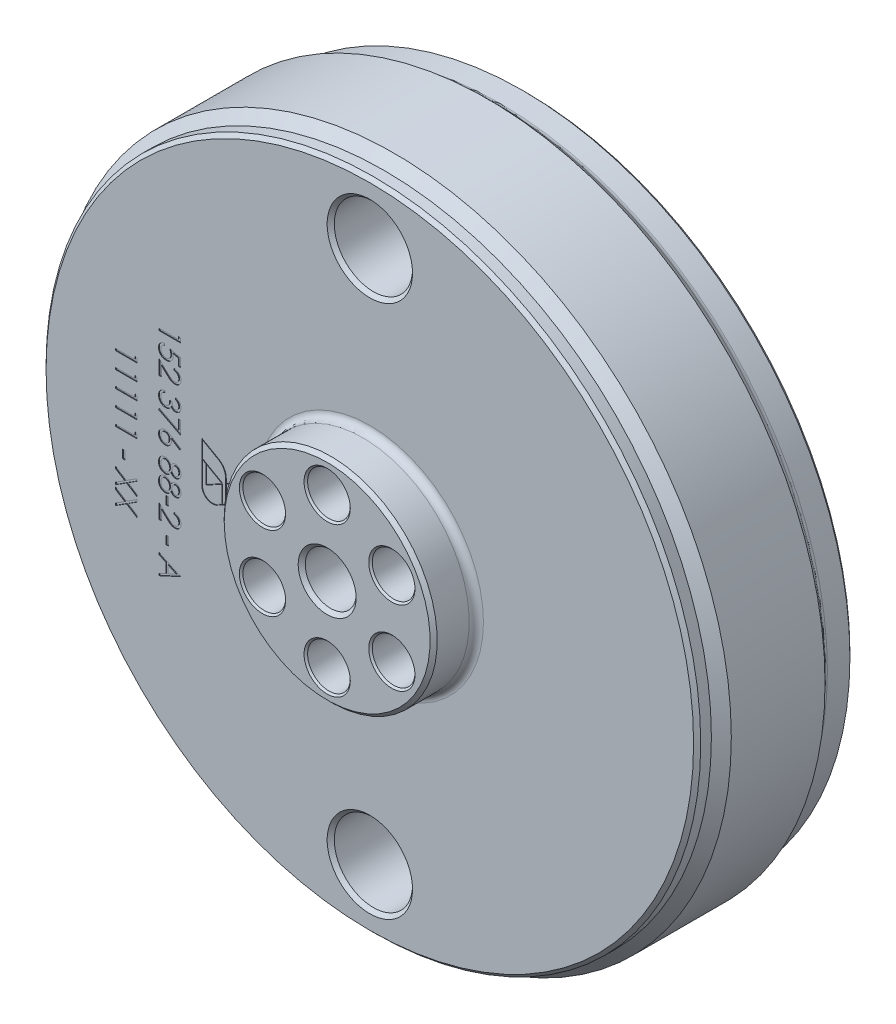
SolidWorks part; units mm, degrees
material "4140 H-T"
ref_plane "Front Plane" through (0, 0, 0) normal (0, 0, 1) x (1, 0, 0)
ref_plane "Top Plane" through (0, 0, 0) normal (0, 1, 0) x (1, 0, 0)
ref_plane "Right Plane" through (0, 0, 0) normal (1, 0, 0) x (0, 0, -1)
sketch "Sketch1" plane through (0, 0, 0) normal (1, 0, 0) x (0, 0, -1)
  line L0 (0, 36.85) -> (0, 45.525)
  line L1 (-0.5, 46.025) -> (-3.6686, 46.025)
  line L2 (-8.2, 6.075) -> (-10.7, 3.575)
  line L4 (-4.2343, 46.2593) -> (-5.4, 47.425)
  line L5 (-5.4, 47.425) -> (-18.58, 47.425)
  line L6 (-18.58, 47.425) -> (-19.98, 46.025)
  line L8 (-27.48, 3.575) -> (-10.7, 3.575)
  line L10 (-27.98, 4.075) -> (-27.48, 3.575)
  line L13 (-19.98, 46.025) -> (-21.48, 46.025)
  line L14 (-21.98, 45.525) -> (-21.98, 15.975)
  line L15 (-22.98, 14.975) -> (-27.48, 14.975)
  line L20 (-27.48, 14.975) -> (-27.98, 14.475)
  line L21 (-27.98, 14.475) -> (-27.98, 4.075)
  line L26 (0, 0) -> (-52.2303, 0) construction
  line L27 (-8.2, 6.075) -> (-8.2, 24.1079)
  line L30 (-21.48, 46.025) -> (-21.98, 45.525)
  line L32 (0, 45.525) -> (-0.5, 46.025)
  arc A0 (-8.2, 24.1079) -> (-1.1714, 35.0297) centre (3.8, 24.1079) cw
  arc A1 (-22.98, 14.975) -> (-21.98, 15.975) centre (-22.98, 15.975) ccw
  arc A5 (-4.2343, 46.2593) -> (-3.6686, 46.025) centre (-3.6686, 46.825) ccw
  arc A6 (0, 36.85) -> (-1.1714, 35.0297) centre (-2, 36.85) cw
  point P1 (0, 46.025)
  point P15 (-21.98, 46.025)
  point P23 (-27.98, 3.575)
  point P44 (-4, 46.025)
  dimension "D32" = 2
  dimension "D34" = 21.98
  dimension "D9" = 12
  dimension "D11" = 1
  dimension "D14" = 0.8
  dimension "D5" = 2.5
  dimension "D1" = 94.85
  dimension "D4" = 7.15
  dimension "D6" = 45
  dimension "D7" = 92.05
  dimension "D8" = 8.2
  dimension "D10" = 6
  dimension "D12" = 29.95
  dimension "D13" = 2
  dimension "D18" = 0.5
  dimension "D20" = 0.5
  dimension "D21" = 92.05
  dimension "D22" = 45
  dimension "D26" = 4
  dimension "D29" = 45
  dimension "D33" = 73.7
  dimension "D36" = 45
revolve "Revolve1" add sketch "Sketch1" angle 360 about L26
cosmetic thread "Cosmetic Thread1" parameters "D2"=93
sketch "Sketch15" plane through (0, 0, 21.98) normal (0, 0, 1) x (1, 0, 0)
  line L0 (0, 0) -> (70.0011, 0) construction
  circle A0 centre (0, 0) radius 37.5 construction
  point P4 (37.5, 0)
  point P8 (0, -37.5)
  point P9 (-37.5, 0)
  point P10 (0, 37.5)
  dimension "D1" = 75
  dimension "D2" = 4
hole_wizard "Ø11.0 (11) Diameter Hole1" positions "Sketch17" profile "Sketch16" hole size "Ø11.0" standard "Ansi Metric"
sketch "Sketch17" plane through (0, 0, 21.98) normal (0, 0, 1) x (1, 0, 0)
  point P2 (0, -37.5)
  point P6 (0, 37.5)
sketch "Sketch16" plane through (0, -37.5, 21.98) normal (1, 0, 0) x (0, -1, 0)
  line L0 (0, 0) -> (0, 13.3047)
  line L1 (0, 13.3047) -> (5.5, 10)
  line L2 (5.5, 10) -> (5.5, 0.5)
  line L3 (5.5, 0.5) -> (6, 0)
  line L5 (6, 0) -> (0, 0)
  line L6 (-5.5, 0.5) -> (-6, 0) construction
  line L10 (0, 13.3047) -> (-5.5, 10) construction
  line L11 (0, -6.35) -> (0, 107.95) construction
  dimension "Hole Dia." = 11
  dimension "Hole Depth" = 10
  dimension "Near C'Sink Dia." = 12
  dimension "Near C'Sink Angle" = 90
  dimension "Drill Angle" = 118
sketch "Sketch19" plane through (0, 0, 27.98) normal (0, 0, 1) x (1, 0, 0)
  circle A0 centre (0, 0) radius 10.5 construction
  point P3 (0, 10.5)
  dimension "D1" = 21
hole_wizard "Ø6.0 (6) Diameter Hole1" positions "Sketch23" profile "Sketch22" hole size "Ø6.0" standard "Ansi Metric" end condition through all
sketch "Sketch23" plane through (0, 0, 27.98) normal (0, 0, 1) x (1, 0, 0)
  point P0 (0, 10.5)
sketch "Sketch22" plane through (0, 10.5, 27.98) normal (1, 0, 0) x (0, -1, 0)
  line L0 (0, 0) -> (0, 19.78)
  line L1 (0, 19.78) -> (3.25, 19.78)
  line L2 (3, 19.53) -> (3, 0.25)
  line L3 (3, 0.25) -> (3.25, 0)
  line L5 (3.25, 0) -> (0, 0)
  line L6 (-3, 0.25) -> (-3.25, 0) construction
  line L7 (3.25, 19.78) -> (3, 19.53)
  line L8 (-3.25, 19.78) -> (-3, 19.53) construction
  line L11 (0, -6.35) -> (0, 107.95) construction
  dimension "Thru Hole Dia." = 6
  dimension "Thru Hole Depth" = 19.78
  dimension "Near C'Sink Dia." = 6.5
  dimension "Near C'Sink Angle" = 90
  dimension "Far C'Sink Dia." = 6.5
  dimension "Far C'Sink Angle" = 90
pattern_circular "CirPattern1" count 6 over 360 about axis through (0, 0, 0) along (0, 0, -1) of "Ø6.0 (6) Diameter Hole1"
sketch "Sketch18" plane through (0, 0, 21.98) normal (0, 0, 1) x (1, 0, 0)
  line L0 (0, 0) -> (-74.7152, 0) construction
  line L1 (0, 0) -> (0, -71.1316) construction
  line L2 (0, 0) -> (82.8113, 0) construction
  line L3 (0, 0) -> (-36.8618, -25.8109) construction
  line L4 (-23.6288, 22.5105) -> (-23.6288, -25.8109) construction
  arc A1 (-45, 0) -> (-36.8618, -25.8109) centre (0, 0) ccw construction
  text T0 "\r\n152 376 88-2 - A\r\n11111 - XX" font "Century Gothic" height 3
  line B0 (-23.6288, -3.1583) -> (-23.6288, 0.1101)
  line B1 (-22.9625, -2.6742) -> (-22.9625, -0.2687)
  line B2 (-23.5288, 0.0533) -> (-23.0625, -0.2119)
  line B3 (-20.1846, -1.1478) -> (-20.1846, -0.5778)
  line B4 (-17.9207, 0.1101) -> (-20.1846, -1.1478)
  line B5 (-22.9625, -2.6742) -> (-20.8153, -1.4897)
  line B6 (-20.8153, -4.1191) -> (-21.3317, -4.4179)
  line B7 (-17.9207, -1.4939) -> (-17.9207, 0.1101)
  line B8 (-20.1846, -3.7752) -> (-20.8153, -4.1191)
  line B9 (-20.1846, -3.7752) -> (-18.728, -2.9113)
  line B10 (-23.6288, 0.1101) -> (-23.6288, 2.6076)
  line B11 (-21.1596, 1.2035) -> (-23.6288, 2.6076)
  line B12 (-20.715, -3.9734) -> (-20.2846, -3.7182)
  line B13 (-18.0207, -1.4939) -> (-18.0207, -0.0598)
  line B14 (-18.0207, -0.0598) -> (-20.1846, -1.2622)
  line B15 (-20.2846, -0.5778) -> (-20.2846, -3.7182)
  line B16 (-21.2114, 1.1179) -> (-23.5288, 2.4357)
  line B17 (-23.5288, 0.1683) -> (-23.5288, 2.4357)
  line B18 (-20.715, -1.4317) -> (-20.715, -3.9734)
  line B19 (-23.5288, 0.1683) -> (-20.715, -1.4317)
  line B20 (-20.8153, -4.0036) -> (-21.3837, -4.3324)
  line B21 (-23.5288, -3.1583) -> (-23.5288, 0.0533)
  line B22 (-20.1846, -1.2622) -> (-20.1846, -3.6589)
  line B23 (-20.1846, -3.6589) -> (-18.779, -2.8253)
  line B24 (-23.0625, -2.8435) -> (-23.0625, -0.2119)
  line B25 (-23.0625, -2.8435) -> (-20.8153, -1.6039)
  line B26 (-20.8153, -1.6039) -> (-20.8153, -4.0036)
  line B27 (-22.9625, -0.2687) -> (-20.8153, -1.4897)
  arc B28 (-18.728, -2.9113) -> (-17.9207, -1.4939) centre (-19.5687, -1.4939) ccw
  arc B29 (-23.6288, -3.1583) -> (-21.3317, -4.4179) centre (-22.1349, -3.1583) ccw
  arc B30 (-20.1846, -0.5778) -> (-21.1596, 1.2035) centre (-22.2993, -0.5778) ccw
  arc B31 (-18.779, -2.8253) -> (-18.0207, -1.4939) centre (-19.5687, -1.4939) ccw
  arc B32 (-20.2846, -0.5778) -> (-21.2114, 1.1179) centre (-22.2993, -0.5778) ccw
  arc B33 (-23.5288, -3.1583) -> (-21.3837, -4.3324) centre (-22.1349, -3.1583) ccw
  dimension "D2" = 45
  dimension "D3" = 35
sketch_block_instance "SKETCH LOGO-1"
sketch_block "SKETCH LOGO" parameters "D1"=29.059, "D2"=11.4163, "D3"=29.624, "D4"=6.8884
extrude "Cut-Extrude1" cut sketch "Sketch18" against normal blind 0.1
